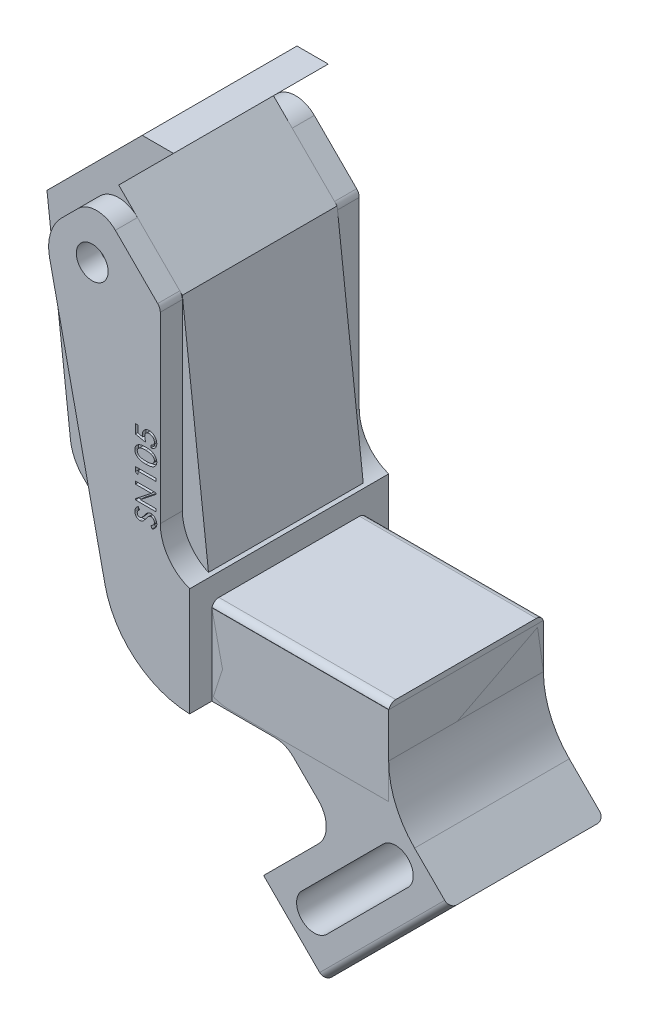
SolidWorks part; units mm, degrees
ref_plane "Front Plane" through (0, 0, 0) normal (0, 0, 1) x (1, 0, 0)
ref_plane "Top Plane" through (0, 0, 0) normal (0, 1, 0) x (1, 0, 0)
ref_plane "Right Plane" through (0, 0, 0) normal (1, 0, 0) x (0, 0, -1)
sketch "Sketch1" plane through (0, 0, 0) normal (0, 0, 1) x (1, 0, 0)
  line L0 (234.037, 26.1653) -> (217.4948, 42.7076)
  line L2 (235.9781, 35.7355) -> (231.7492, 72.4742)
  line L3 (227.1783, 77.0451) -> (213.7079, 63.5748) construction
  line L9 (215.6766, 46.4716) -> (213.7079, 63.5748)
  line L10 (231.7492, 72.4742) -> (222.6073, 81.6161)
  line L11 (213.7079, 63.5748) -> (212.3007, 75.7996)
  line L12 (222.6073, 81.6161) -> (212.7642, 71.773) construction
  line L21 (261.3781, 24.3055) -> (238.5272, 24.3055)
  line L26 (230.474, 89.4828) -> (225.9839, 89.4828)
  line L27 (225.9839, 89.4828) -> (212.3007, 75.7996)
  line L29 (230.474, 89.4828) -> (222.6073, 81.6161)
  line L31 (235.9781, 35.7355) -> (261.3781, 35.7355)
  line L32 (261.3781, 35.7355) -> (261.3781, 24.3055)
  arc A0 (217.4948, 42.7076) -> (215.6766, 46.4716) centre (221.9849, 47.1977) cw
  arc A1 (234.037, 26.1653) -> (238.5272, 24.3055) centre (238.5272, 30.6555) ccw
  point P18 (235.8969, 24.3055)
  dimension "D1" = 19.05
  dimension "D3" = 6.35
  dimension "D2" = 3.175
  dimension "D4" = 12.9286
  dimension "D6" = 25.4
extrude "Boss-Extrude1" add sketch "Sketch1" along normal mid plane 22.225 contours L10 L29 L26 L27 region at (230.5603, 50.5284, 0)
sketch "Sketch2" plane through (0, 0, 0) normal (0, 0, 1) x (1, 0, 0)
  line L0 (233.3024, 24.1041) -> (225.9839, 24.1041)
  line L1 (261.3781, 35.7355) -> (261.3781, 24.3055) construction
  line L2 (247.3337, 24.1041) -> (261.3781, 24.1041)
  line L4 (247.3337, 36.4993) -> (261.3781, 36.4993)
  line L9 (261.3781, 24.1041) -> (261.3781, 36.4993)
  line L10 (231.7502, 72.4732) -> (222.6073, 81.6161)
  line L11 (247.3337, 36.4993) -> (231.7502, 36.4993)
  line L12 (222.6073, 81.6161) -> (205.3293, 64.3381) construction
  line L14 (225.9839, 24.1041) -> (215.1237, 74.1324)
  line L15 (222.6073, 81.6161) -> (215.1237, 74.1324)
  line L21 (247.3337, 24.1041) -> (233.3024, 24.1041)
  line L31 (231.7502, 36.4993) -> (231.7502, 72.4732)
  dimension "D1" = 12.93
  dimension "D6" = 12.3952
extrude "Boss-Extrude2" add sketch "Sketch2" along normal mid plane 22.225 separate body
fillet "Fillet6" radius 3.175 1 edges at (231.7502, 36.4993, 0)
fillet "Fillet7" radius 12.7 1 edges at (225.9839, 24.1041, 0)
sketch "Sketch3" plane through (0, 0, 0) normal (0, 0, 1) x (1, 0, 0)
  circle A1 centre (221.9787, 73.2645) radius 2.286
extrude "Cut-Extrude1" cut sketch "Sketch3" against normal through all both and the other way through all
fillet "Fillet9" radius 6.35 1 edges at (215.1237, 74.1324, 0)
sketch "Sketch4" plane through (0, 0, 11.1125) normal (0, 0, 1) x (1, 0, 0)
  line L0 (261.3781, 30.3017) -> (235.9781, 30.3017) construction
  line L1 (235.9781, 36.4969) -> (235.9781, 24.1064)
  line L2 (235.9781, 36.4969) -> (235.9781, 36.4993)
  line L7 (222.6073, 81.6161) -> (217.5742, 76.583)
  line L8 (215.8588, 70.7457) -> (223.8118, 34.1099)
  line L9 (236.2228, 24.1041) -> (261.3781, 24.1041)
  line L10 (261.3781, 24.1041) -> (261.3781, 36.4993)
  line L11 (261.3781, 36.4993) -> (234.9252, 36.4993)
  line L12 (231.7502, 39.6743) -> (231.7502, 72.4732)
  line L13 (231.7502, 72.4732) -> (222.6073, 81.6161)
  line L14 (222.6073, 81.6161) -> (217.5742, 76.583)
  line L15 (215.8588, 70.7457) -> (223.8118, 34.1099)
  line L16 (236.2228, 24.1041) -> (261.3781, 24.1041)
  line L17 (261.3781, 24.1041) -> (261.3781, 36.4993)
  line L18 (261.3781, 36.4993) -> (234.9252, 36.4993)
  line L19 (231.7502, 39.6743) -> (231.7502, 72.4732)
  line L20 (231.7502, 72.4732) -> (222.6073, 81.6161)
  arc A3 (217.5742, 76.583) -> (215.8588, 70.7457) centre (222.0643, 72.0928) ccw
  arc A4 (223.8118, 34.1099) -> (236.2228, 24.1041) centre (236.2228, 36.8041) ccw
  arc A5 (231.7502, 39.6743) -> (234.9252, 36.4993) centre (234.9252, 39.6743) ccw
  arc A6 (217.5742, 76.583) -> (215.8588, 70.7457) centre (222.0643, 72.0928) ccw
  arc A7 (223.8118, 34.1099) -> (236.2228, 24.1041) centre (236.2228, 36.8041) ccw
  arc A8 (231.7502, 39.6743) -> (234.9252, 36.4993) centre (234.9252, 39.6743) ccw
  point P16 (235.9781, 30.3017)
  circle M12 centre (221.9787, 73.2645) radius 2.286
  line M13 (222.6073, 81.6161) -> (217.5742, 76.583)
  arc M14 (217.5742, 76.583) -> (215.8588, 70.7457) centre (222.0643, 72.0928) ccw
  line M15 (215.8588, 70.7457) -> (223.8118, 34.1099)
  arc M16 (223.8118, 34.1099) -> (236.2228, 24.1041) centre (236.2228, 36.8041) ccw
  line M19 (261.3781, 36.4993) -> (234.9252, 36.4993)
  arc M20 (234.9252, 36.4993) -> (231.7502, 39.6743) centre (234.9252, 39.6743) cw
  line M21 (231.7502, 39.6743) -> (231.7502, 72.4732)
  line M22 (231.7502, 72.4732) -> (222.6073, 81.6161)
  dimension "D2" = 25.4
  dimension "D1" = 0
extrude "Boss-Extrude3" add sketch "Sketch4" along normal blind 3.175 contours L1 L2 M19 M20 M21 M22 M13 M14 M15 M16 M12 region at (226.1864, 53.5405, 11.1125)
mirror "Mirror1" about plane through (0, 0, 0) normal (0, 0, 1) of "Boss-Extrude3"
sketch "Sketch6" plane through (0, 0, 14.2875) normal (0, 0, 1) x (1, 0, 0)
  line L0 (235.9781, 36.4993) -> (235.9781, 39.6743)
  line L1 (235.9781, 39.6743) -> (231.7502, 39.6743)
  line L6 (235.9781, 24.1064) -> (235.9781, 36.4993)
  line L7 (235.9781, 36.4993) -> (234.9252, 36.4993)
  line L8 (231.7502, 39.6743) -> (231.7502, 72.4732)
  line L9 (231.7502, 72.4732) -> (222.6073, 81.6161)
  line L10 (222.6073, 81.6161) -> (217.5742, 76.583)
  line L11 (215.8588, 70.7457) -> (223.8118, 34.1099)
  line L12 (235.9781, 24.1064) -> (235.9781, 36.4993)
  line L13 (235.9781, 36.4993) -> (234.9252, 36.4993)
  line L14 (231.7502, 39.6743) -> (231.7502, 72.4732)
  line L15 (231.7502, 72.4732) -> (222.6073, 81.6161)
  line L16 (222.6073, 81.6161) -> (217.5742, 76.583)
  line L17 (215.8588, 70.7457) -> (223.8118, 34.1099)
  arc A3 (231.7502, 39.6743) -> (234.9252, 36.4993) centre (234.9252, 39.6743) ccw
  arc A4 (217.5742, 76.583) -> (215.8588, 70.7457) centre (222.0643, 72.0928) ccw
  arc A5 (223.8118, 34.1099) -> (235.9781, 24.1064) centre (236.2228, 36.8041) ccw
  arc A6 (231.7502, 39.6743) -> (234.9252, 36.4993) centre (234.9252, 39.6743) ccw
  arc A7 (217.5742, 76.583) -> (215.8588, 70.7457) centre (222.0643, 72.0928) ccw
  arc A8 (223.8118, 34.1099) -> (235.9781, 24.1064) centre (236.2228, 36.8041) ccw
  line M12 (235.9781, 36.4993) -> (234.9252, 36.4993)
  arc M13 (234.9252, 36.4993) -> (231.7502, 39.6743) centre (234.9252, 39.6743) cw
  dimension "D1" = 0
extrude "Boss-Extrude4" add sketch "Sketch6" against normal up to surface (28.575 mm away) contours L0 L1 M13 M12 region at (234.134, 38.2555, 14.2875) up to face at (224.2647, 73.2645, -14.2875)
fillet "Fillet10" radius 6.35 1 edges at (231.7502, 39.6743, 0)
sketch "Sketch7" plane through (152.1117, 152.1117, 0) normal (0.7071, 0.7071, 0) x (0, 0, -1)
  line L0 (-11.1125, -141.0528) -> (-11.1125, -99.6959)
  line L1 (11.1125, -141.0528) -> (11.1125, -99.6959)
  line L2 (-11.1125, -112.6259) -> (11.1125, -112.6259)
  line L3 (11.1125, -112.6259) -> (14.2875, -112.6259)
  line L4 (-14.2875, -112.6259) -> (14.2875, -112.6259)
  line L5 (14.2875, -112.6259) -> (14.2875, -99.6959)
  line L6 (14.2875, -99.6959) -> (-14.2875, -99.6959)
  line L7 (-14.2875, -99.6959) -> (-14.2875, -112.6259)
  line L8 (-14.2875, -112.6259) -> (-11.1125, -112.6259)
  line L9 (14.2875, -112.6259) -> (14.2875, -99.6959)
  line L10 (14.2875, -99.6959) -> (-14.2875, -99.6959)
  line L11 (-14.2875, -99.6959) -> (-14.2875, -112.6259)
  line M5 (-14.2875, -112.6259) -> (14.2875, -112.6259)
  line M7 (14.2875, -99.6959) -> (-14.2875, -99.6959)
  dimension "D1" = 0
extrude "Cut-Extrude4" cut sketch "Sketch7" against normal through all contours L1 L0 M5 M7 | L0 L2 L1 M5 region at (227.1788, 77.0446, 0)
fillet "Fillet11" radius 1.016 2 edges at (248.6781, 36.4993, -11.1125) (248.6781, 36.4993, 11.1125)
sketch "Sketch9" plane through (0, 0, -11.1125) normal (0, 0, 1) x (1, 0, 0)
  line L0 (219.7199, 60.4429) -> (216.5192, 75.187)
  line L5 (231.7502, 72.4732) -> (222.6073, 81.6161)
  line L6 (222.6073, 81.6161) -> (217.5742, 76.583)
  line L7 (215.8588, 70.7457) -> (218.3852, 59.1081)
  line L8 (218.3852, 59.1081) -> (231.7502, 72.4732)
  line L10 (231.7502, 72.4732) -> (222.6073, 81.6161)
  line L11 (222.6073, 81.6161) -> (217.5742, 76.583)
  line L12 (215.8588, 70.7457) -> (218.3852, 59.1081)
  line L13 (218.3852, 59.1081) -> (231.7502, 72.4732)
  arc A1 (217.5742, 76.583) -> (215.8588, 70.7457) centre (222.0643, 72.0928) ccw
  arc A2 (217.5742, 76.583) -> (215.8588, 70.7457) centre (222.0643, 72.0928) ccw
  arc M11 (217.5742, 76.583) -> (215.8588, 70.7457) centre (222.0643, 72.0928) ccw
  line M12 (215.8588, 70.7457) -> (218.3852, 59.1081)
  line M13 (218.3852, 59.1081) -> (231.7502, 72.4732)
  dimension "D2" = 1.5875
  dimension "D1" = 0
extrude "Boss-Extrude5" add sketch "Sketch9" along normal up to surface (22.225 mm away) contours L0 M13 M11 M12 region at (217.5523, 66.7855, -11.1125) up to face at (221.0862, 72.149, 11.1125)
fillet "Fillet12" radius 0.254 1 edges at (216.5192, 75.187, 0) tangent propagation no
sketch "Sketch10" plane through (0, 0, 11.1125) normal (0, 0, 1) x (1, 0, 0)
  line L0 (261.3781, 24.1041) -> (270.1428, 15.3394)
  line L1 (270.1428, 15.3394) -> (252.1823, -2.6212)
  line L2 (222.6073, 81.6161) -> (217.5742, 76.583) construction
  line L3 (261.3781, 24.1041) -> (261.3781, 36.4993)
  line L4 (252.1823, -2.6212) -> (243.4176, 6.1436)
  line L6 (245.0124, 24.1044) -> (235.9781, 24.1064)
  line L7 (236.2228, 24.1041) -> (261.3781, 24.1041) construction
  line L8 (261.3781, 24.1041) -> (246.5833, 24.1041)
  line L9 (247.6974, 22.9967) -> (251.2927, 19.4233)
  line L10 (251.3009, 14.0269) -> (243.4176, 6.1436)
  arc A0 (247.6974, 22.9967) -> (245.0124, 24.1044) centre (245.0116, 20.2944) ccw
  arc A1 (251.2927, 19.4233) -> (251.3009, 14.0269) centre (248.6069, 16.721) cw
  line M14 (236.2228, 24.1041) -> (261.3781, 24.1041)
  dimension "D2" = 3.81
  dimension "D1" = 25.4
extrude "Boss-Extrude6" add sketch "Sketch10" against normal up to surface (22.225 mm away) contours L4 L1 L0 M14 region at (256.3296, 12.3982, 11.1125) up to face at (246.187, 28.6561, -11.1125)
fillet "Fillet13" radius 12.7 1 edges at (261.3781, 24.1041, 0)
fillet "Fillet14" radius 1.016 2 edges at (261.1626, 6.3591, -11.1125) (261.1626, 6.3591, 11.1125)
sketch "Sketch8" plane through (0, 0, 11.1125) normal (0, 0, 1) x (1, 0, 0)
  line L0 (261.3781, 29.9461) -> (235.9781, 29.9461) construction
  line L1 (261.3781, 29.3646) -> (261.3781, 35.4833) construction
  line L2 (235.9781, 35.4833) -> (235.9781, 24.1064) construction
  line L3 (236.2228, 24.1041) -> (245.0632, 24.1041) construction
  line L4 (246.7731, 29.9461) -> (240.4231, 29.9461) construction
  line L5 (246.7731, 27.4061) -> (240.4231, 27.4061)
  line L6 (246.7731, 32.4861) -> (240.4231, 32.4861)
  line L7 (262.3659, 16.8301) -> (250.6916, 5.1557) construction
  line L8 (264.162, 15.034) -> (252.4877, 3.3597)
  line L9 (260.5699, 18.6261) -> (248.8956, 6.9518)
  line L10 (247.5485, 2.0127) -> (265.509, 19.9732) construction
  line L11 (251.4639, -1.9027) -> (243.4176, 6.1436) construction
  line L12 (251.3009, 14.0269) -> (243.4176, 6.1436) construction
  line L13 (265.0979, 20.3843) -> (269.4244, 16.0578) construction
  arc A0 (246.7731, 27.4061) -> (246.7731, 32.4861) centre (246.7731, 29.9461) ccw
  arc A1 (240.4231, 32.4861) -> (240.4231, 27.4061) centre (240.4231, 29.9461) ccw
  arc A2 (264.162, 15.034) -> (260.5699, 18.6261) centre (262.3659, 16.8301) ccw
  arc A3 (248.8956, 6.9518) -> (252.4877, 3.3597) centre (250.6916, 5.1557) ccw
  point P10 (243.5981, 29.9461)
  point P17 (256.5288, 10.9929)
  dimension "D2" = 2.54
  dimension "D1" = 5.842
  dimension "D3" = 6.35
  dimension "D4" = 14.605
  dimension "D5" = 5.842
  dimension "D6" = 4.445
extrude "Cut-Extrude5" cut sketch "Sketch8" against normal through all
fillet "Fillet15" radius 3.81 2 edges at (222.6073, 81.6161, -12.7) (222.6073, 81.6161, 12.7)
fillet "Fillet16" radius 3.81 1 edges at (219.7199, 60.4429, 0)
fillet "Fillet17" radius 1.27 1 edges at (231.7502, 72.4732, 0) tangent propagation no
fillet "Fillet18" radius 1.27 2 edges at (231.7502, 72.4732, -12.7) (231.7502, 72.4732, 12.7)
sketch "Sketch11" plane through (0, 0, 14.2875) normal (0, 0, 1) x (1, 0, 0)
  line L0 (231.172, 75.8836) -> (231.172, 25.1516) construction
  arc A2 (223.8118, 34.1099) -> (235.9781, 24.1064) centre (236.2228, 36.8041) ccw construction
  text T0 "<b>SN105</b>" font "Century Gothic" height 3
  point P4 (229.6009, 29.7632)
  point P5 (228.1569, 26.9943)
  point P6 (0, 0)
  point P7 (228.3398, 26.9943)
  point P12 (0, 0)
extrude "Cut-Extrude6" cut sketch "Sketch11" against normal blind 0.5
sketch "Sketch12" plane through (0, 0, -14.2875) normal (0, 0, -1) x (-1, 0, 0)
  line L0 (-231.172, 75.8836) -> (-231.172, 25.1516) construction
  line L1 (-231.172, 75.8836) -> (-231.172, 25.1516) construction
  text T0 "<b>SN105</b>" font "Century Gothic" height 3
extrude "Cut-Extrude7" cut sketch "Sketch12" against normal blind 0.5
